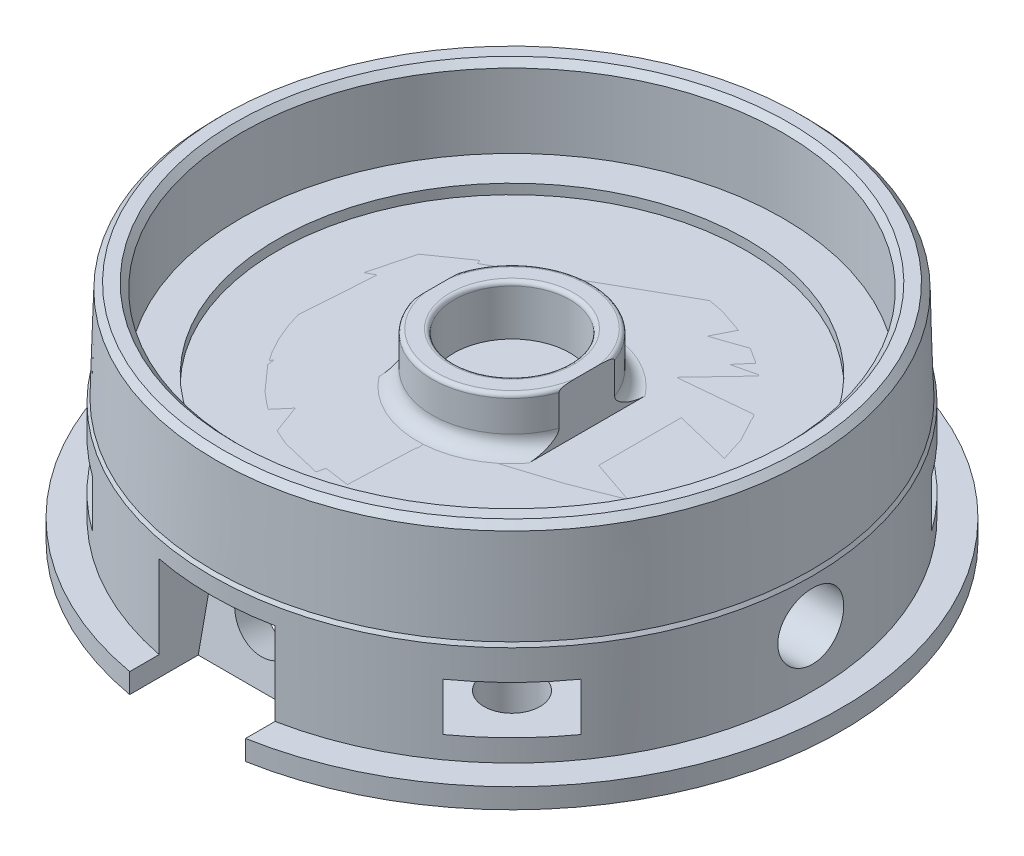
SolidWorks part; units mm, degrees
ref_plane "Front Plane" through (0, 0, 0) normal (0, 0, 1) x (1, 0, 0)
ref_plane "Top Plane" through (0, 0, 0) normal (0, 1, 0) x (1, 0, 0)
ref_plane "Right Plane" through (0, 0, 0) normal (1, 0, 0) x (0, 0, -1)
sketch "Sketch1" plane through (0, 0, 0) normal (0, 1, 0) x (1, 0, 0)
  circle A0 centre (0, 0) radius 15.05
  dimension "D1" = 30.1
extrude "Boss-Extrude1" add sketch "Sketch1" along normal blind 6.2
sketch "Sketch2" plane through (0, 6.2, 0) normal (0, 1, 0) x (1, 0, 0)
  circle A0 centre (0, 0) radius 11.75
  dimension "D1" = 23.5
extrude "Cut-Extrude1" cut sketch "Sketch2" against normal blind 0.5
sketch "Sketch3" plane through (0, 6.2, 0) normal (0, 1, 0) x (1, 0, 0)
  circle A0 centre (0, 0) radius 13.575
  circle A1 centre (0, 0) radius 15.05
  circle A2 centre (0, 0) radius 15.05 construction
  dimension "D1" = 27.15
extrude "Boss-Extrude2" add sketch "Sketch3" along normal blind 4
sketch "Sketch4" plane through (0, 5.7, 0) normal (0, 1, 0) x (1, 0, 0)
  circle A0 centre (0, 0) radius 1.65
  dimension "D1" = 3.3
extrude "Cut-Extrude2" cut sketch "Sketch4" against normal through all
ref_plane "Plane1" through (3.75, 0, 0) normal (1, 0, 0) x (0, 0, -1)
sketch "Sketch5" plane through (0, 0, 0) normal (1, 0, 0) x (0, 0, -1)
  line L1 (1.65, 5.7) -> (-1.65, 5.7) construction
  line L2 (-2.875, -0.05) -> (2.875, -0.05) construction
  line L3 (-2.875, -0.05) -> (-2.875, 5.7) construction
  line L4 (-2.875, 5.7) -> (2.875, 5.7) construction
  line L5 (2.875, -0.05) -> (2.875, 5.7) construction
  line L6 (-2.875, -0.05) -> (2.875, 5.7) construction
  line L7 (-2.875, 5.7) -> (2.875, -0.05) construction
  circle A0 centre (0, 2.825) radius 1.65
  dimension "D1" = 3.3
  dimension "D2" = 5.75
extrude "Cut-Extrude3" cut sketch "Sketch5" along normal through all
sketch "Sketch6" plane through (0, 0, 0) normal (0, -1, 0) x (1, 0, 0)
  circle A0 centre (0, 0) radius 1.65 construction
  circle A1 centre (0, 0) radius 1.65
  circle A2 centre (0, 0) radius 16.5
  dimension "D1" = 33
extrude "Boss-Extrude3" add sketch "Sketch6" along normal blind 1
sketch "Sketch7" plane through (3.75, 0, 0) normal (1, 0, 0) x (0, 0, -1)
  line L7 (-2.875, 5.7) -> (2.875, 5.7)
  line L8 (-2.875, 5.7) -> (-2.875, -0.05)
  line L9 (-2.875, -0.05) -> (2.875, -0.05)
  line L10 (2.875, 5.7) -> (2.875, -0.05)
  line L11 (-2.875, 5.7) -> (2.875, -0.05) construction
  line L12 (-2.875, -0.05) -> (2.875, 5.7) construction
  point P1 (0, 2.825)
  dimension "D2" = 5.75
extrude "Cut-Extrude4" cut sketch "Sketch7" along normal blind 1.85
ref_axis "Axis1" through (0, 10.2, 0) along (0, -1, 0)
pattern_circular "CirPattern1" count 2 over 360 about axis through (0, 10.2, 0) along (0, -1, 0) of "Cut-Extrude4", "Cut-Extrude3"
ref_plane "Plane2" through (0, 0, 0) normal (0, 0, 1) x (0, -1, 0)
ref_plane "Plane3" through (0, 0, 12.6) normal (0, 0, 1) x (0, -1, 0)
sketch "Sketch11" plane through (0, 0, 12.6) normal (0, 0, 1) x (0, -1, 0)
  line L0 (0, 23.2225) -> (0, -23.2225) construction
  point P4 (0, 0)
ref_plane "Plane4" through (0, 2.5624, 12.0553) normal (0, 0.2079, 0.9781) x (-1, 0, 0)
sketch "Sketch9" plane through (0, 0.4393, 12.5066) normal (0, 0.2079, 0.9781) x (0, -0.9781, 0.2079)
  line L0 (-12.1477, 0) -> (-2.1706, 0) construction
  line L2 (1.4491, 2.9) -> (-4.3509, 2.9) construction
  line L3 (1.4491, 2.9) -> (1.4491, -2.9) construction
  line L4 (1.4491, -2.9) -> (-4.3509, -2.9) construction
  line L5 (-4.3509, 2.9) -> (-4.3509, -2.9) construction
  line L6 (1.4491, 2.9) -> (-4.3509, -2.9) construction
  line L7 (1.4491, -2.9) -> (-4.3509, 2.9) construction
  line L8 (0.4491, 23.2225) -> (0.4491, -23.2225) construction
  circle A0 centre (-1.4509, 0) radius 1.65
  dimension "D2" = 3.3
  dimension "D1" = 5.8
  dimension "D3" = 1
extrude "Cut-Extrude5" cut sketch "Sketch9" along normal through all and the other way blind 2
sketch "Sketch10" plane through (0, 0.0203, 12.5957) normal (0, 0.2079, 0.9781) x (0, -0.9781, 0.2079)
  line L1 (1.0208, 2.9) -> (-4.7792, 2.9) construction
  line L2 (-4.7792, 2.9) -> (-4.7792, -2.9) construction
  line L3 (1.0208, -2.9) -> (-4.7792, -2.9) construction
  line L5 (1.0208, 2.9) -> (-4.7792, 2.9)
  line L6 (-4.7792, 2.9) -> (-4.7792, -2.9)
  line L7 (1.0208, -2.9) -> (-4.7792, -2.9)
  line L8 (1.0208, 2.9) -> (3.0208, 2.9)
  line L9 (3.0208, 2.9) -> (3.0208, -2.9)
  line L10 (3.0208, -2.9) -> (1.0208, -2.9)
  dimension "D1" = 2
extrude "Cut-Extrude6" cut sketch "Sketch10" along normal blind 1.8
ref_plane "Plane5" through (0, 2.2506, 10.5881) normal (0, 0.2079, 0.9781) x (-1, 0, 0)
sketch "Sketch13" plane through (0, 2.2506, 10.5881) normal (0, 0.2079, 0.9781) x (-1, 0, 0)
  line L0 (-2.0203, -0.0157) -> (-3.3435, 3.6197)
  line L1 (-3.3435, 3.6197) -> (3.3435, 3.6197)
  line L2 (3.3435, 3.6197) -> (2.0203, -0.0157)
  line L3 (0, 0.7197) -> (0, 3.6197) construction
  line L4 (-2.9, 3.6197) -> (2.9, 3.6197) construction
  circle A0 centre (0, 0.7197) radius 1.65 construction
  circle A1 centre (0, 0.7197) radius 1.65 construction
  circle A2 centre (0, 0.7197) radius 2.15 construction
  arc A3 (2.0203, -0.0157) -> (-2.0203, -0.0157) centre (0, 0.7197) cw
  dimension "D1" = 20
  dimension "D2" = 0.5
ref_plane "Plane6" through (0, 0, 0) normal (-1, 0, 0) x (0, -1, 0)
ref_plane "Plane7" through (0, 0, 15.05) normal (0, 0, 1) x (1, 0, 0)
sketch "Sketch14" plane through (0, 0, 0) normal (-1, 0, 0) x (0, -1, 0)
  line L0 (-3.1606, 10.3947) -> (3.3348, 0) construction
  line L3 (0.0673, 11.0808) -> (-3.1606, 10.3947) construction
  line L5 (-3.1606, 10.3947) -> (-0.9781, 0.1272) construction
  arc A0 (-3.1606, 10.3947) -> (3.3348, 0) centre (14.3667, 14.1202) ccw
  dimension "D1" = 70
sweep "Cut-Sweep1" cut profiles "Sketch13" path "Sketch14"
sketch "Sketch19" plane through (0, 0, 15.05) normal (0, 0, 1) x (1, 0, 0)
  line L0 (2.9, 5.0693) -> (-2.9, 5.0693) construction
  line L1 (2.9, 5.0693) -> (-2.9, 5.0693) construction
  line L2 (15.05, 0) -> (-15.05, 0) construction
  line L3 (2.9, 0) -> (-2.9, 0) construction
  line L4 (-2.9, 5.0693) -> (-2.9, 0) construction
  line L5 (2.9, 5.0693) -> (2.9, 0) construction
  line L6 (-2.9, 4.1501) -> (2.9, 4.1501)
  line L7 (2.9, 4.1501) -> (2.9, 0)
  line L8 (2.9, 0) -> (-2.9, 0)
  line L9 (-2.9, 0) -> (-2.9, 4.1501)
  spline S0 degree 3 poles (-0.1103, 0.7763) (0.2206, 0.7763) (0.4399, 0.8212) (0.8405, 0.99) (1.0254, 1.1159) (1.2534, 1.3496) (1.3227, 1.4364) (1.4409, 1.6193) (1.4906, 1.7158) (1.5713, 1.9192) (1.6017, 2.0256) (1.6413, 2.2394) (1.6508, 2.3479) (1.6481, 2.6783) (1.6048, 2.894) (1.4812, 3.1989) (1.4311, 3.2954) (1.313, 3.4783) (1.2443, 3.5654) (1.0179, 3.8015) (0.8351, 3.9301) (0.4362, 4.1039) (0.2169, 4.1502) (-0.1103, 4.15) (-0.221, 4.1383) (-0.434, 4.0932) (-0.5375, 4.06) (-0.8386, 3.9282) (-1.0184, 3.8015) (-1.2465, 3.5629) (-1.3137, 3.4774) (-1.4314, 3.2948) (-1.4822, 3.1968) (-1.5642, 2.9938) (-1.5952, 2.8896) (-1.6378, 2.6758) (-1.6492, 2.5653) (-1.6515, 2.2381) (-1.6107, 2.0182) (-1.4501, 1.6141) (-1.3285, 1.4262) (-1.1006, 1.193) (-1.0155, 1.1218) (-0.835, 0.9992) (-0.7396, 0.9474) (-0.5381, 0.8627) (-0.4321, 0.8302) (-0.2188, 0.7873) (-0.1103, 0.7763) (0.2206, 0.7763) (0.4399, 0.8212) knots -0.03125 -0.03125 0 0 0.0625 0.0625 0.125 0.125 0.15625 0.15625 0.1875 0.1875 0.21875 0.21875 0.25 0.25 0.3125 0.3125 0.34375 0.34375 0.375 0.375 0.4375 0.4375 0.5 0.5 0.53125 0.53125 0.5625 0.5625 0.625 0.625 0.65625 0.65625 0.6875 0.6875 0.71875 0.71875 0.75 0.75 0.8125 0.8125 0.875 0.875 0.90625 0.90625 0.9375 0.9375 0.96875 0.96875 1 1 1.0625 1.0625 1.125 only from (0, 0.7763) to (0, 0.7763) construction
  spline S1 degree 3 poles (-0.1103, 0.7763) (0.2206, 0.7763) (0.4399, 0.8212) (0.8405, 0.99) (1.0254, 1.1159) (1.2534, 1.3496) (1.3227, 1.4364) (1.4409, 1.6193) (1.4906, 1.7158) (1.5713, 1.9192) (1.6017, 2.0256) (1.6413, 2.2394) (1.6508, 2.3479) (1.6481, 2.6783) (1.6048, 2.894) (1.4812, 3.1989) (1.4311, 3.2954) (1.313, 3.4783) (1.2443, 3.5654) (1.0179, 3.8015) (0.8351, 3.9301) (0.4362, 4.1039) (0.2169, 4.1502) (-0.1103, 4.15) (-0.221, 4.1383) (-0.434, 4.0932) (-0.5375, 4.06) (-0.8386, 3.9282) (-1.0184, 3.8015) (-1.2465, 3.5629) (-1.3137, 3.4774) (-1.4314, 3.2948) (-1.4822, 3.1968) (-1.5642, 2.9938) (-1.5952, 2.8896) (-1.6378, 2.6758) (-1.6492, 2.5653) (-1.6515, 2.2381) (-1.6107, 2.0182) (-1.4501, 1.6141) (-1.3285, 1.4262) (-1.1006, 1.193) (-1.0155, 1.1218) (-0.835, 0.9992) (-0.7396, 0.9474) (-0.5381, 0.8627) (-0.4321, 0.8302) (-0.2188, 0.7873) (-0.1103, 0.7763) (0.2206, 0.7763) (0.4399, 0.8212) knots -0.03125 -0.03125 0 0 0.0625 0.0625 0.125 0.125 0.15625 0.15625 0.1875 0.1875 0.21875 0.21875 0.25 0.25 0.3125 0.3125 0.34375 0.34375 0.375 0.375 0.4375 0.4375 0.5 0.5 0.53125 0.53125 0.5625 0.5625 0.625 0.625 0.65625 0.65625 0.6875 0.6875 0.71875 0.71875 0.75 0.75 0.8125 0.8125 0.875 0.875 0.90625 0.90625 0.9375 0.9375 0.96875 0.96875 1 1 1.0625 1.0625 1.125 only from (0, 0.7763) to (0, 0.7763) construction
extrude "Cut-Extrude11" cut sketch "Sketch19" against normal up to surface (0.6098 mm away) up to face at (0, 2.0347, 14.0077)
pattern_circular "CirPattern2" count 2 over 360 about axis through (0, 10.2, 0) along (0, -1, 0) of "Cut-Extrude5", "Cut-Sweep1", "Cut-Extrude6", "Cut-Extrude11"
sketch "Sketch16" plane through (0, -1, 0) normal (0, -1, 0) x (1, 0, 0)
  line L0 (0, 0) -> (-11.6673, 11.6673) construction
  line L1 (0, 11.1539) -> (0, -11.1539) construction
  circle A0 centre (0, 0) radius 16.5 construction
  circle A1 centre (-8.5913, 8.5913) radius 1.4
  circle A2 centre (-8.5913, 8.5913) radius 2.9 construction
  circle A3 centre (0, 0) radius 15.05 construction
  dimension "D2" = 2.8
  dimension "D3" = 5.8
  dimension "D1" = 45
extrude "Cut-Extrude8" cut sketch "Sketch16" against normal blind 4.5
sketch "Sketch17" plane through (0, 3.5, 0) normal (0, -1, 0) x (1, 0, 0)
  line L1 (-10.5918, 10.5918) -> (-11.324, 7.8591) construction
  line L2 (-11.324, 7.8591) -> (-9.3236, 5.8587)
  line L3 (-9.3236, 5.8587) -> (-6.5909, 6.5909)
  line L4 (-6.5909, 6.5909) -> (-5.8587, 9.3236)
  line L5 (-5.8587, 9.3236) -> (-7.8591, 11.324)
  line L6 (-7.8591, 11.324) -> (-10.5918, 10.5918) construction
  line L7 (-7.8591, 11.324) -> (-8.9095, 12.3744)
  line L8 (-8.9095, 12.3744) -> (-12.3744, 8.9095)
  line L9 (-12.3744, 8.9095) -> (-11.324, 7.8591)
  line L10 (-6.5909, 6.5909) -> (-8.5913, 8.5913) construction
  circle A0 centre (-8.5913, 8.5913) radius 2.45 construction
  circle A1 centre (0, 0) radius 15.05 construction
  dimension "D1" = 4.9
extrude "Cut-Extrude9" cut sketch "Sketch17" along normal blind 2.4
pattern_circular "CirPattern3" count 4 over 360 about axis through (0, 10.2, 0) along (0, -1, 0) of "Cut-Extrude8", "Cut-Extrude9"
sketch "Sketch18" plane through (0, 5.7, 0) normal (0, 1, 0) x (1, 0, 0)
  circle A2 centre (0, 0) radius 2.9
  dimension "D1" = 5.8
extrude "Cut-Extrude10" cut sketch "Sketch18" against normal blind 0.7
sketch "Sketch20" plane through (0, 5.7, 0) normal (0, 1, 0) x (1, 0, 0)
  line L0 (3.75, 2.875) -> (3.75, -2.875) construction
  line L1 (-3.75, -2.875) -> (-3.75, 2.875) construction
  line L2 (3.75, 1.3919) -> (3.75, -1.3919)
  line L3 (-3.75, -1.3919) -> (-3.75, 1.3919)
  circle A0 centre (0, 0) radius 2.9 construction
  circle A1 centre (0, 0) radius 2.9
  arc A2 (3.75, 1.3919) -> (-3.75, 1.3919) centre (0, 0) ccw
  arc A3 (-3.75, -1.3919) -> (3.75, -1.3919) centre (0, 0) ccw
  dimension "D1" = 8
extrude "Boss-Extrude4" add sketch "Sketch20" along normal blind 2.5
fillet "Fillet2" radius 0.75 2 edges at (0, 5.7, 4) (0, 5.7, -4)
fillet "Fillet3" radius 0.2 3 edges at (0, 8.2, 4) (0, 8.2, -4) (0, 8.2, 2.9)
sketch "Sketch21" plane through (0, 0, 0) normal (0, 0, 1) x (1, 0, 0)
  line L0 (13.575, 6.2) -> (-13.575, 6.2) construction
  line L1 (13.575, 6.2) -> (-13.575, 6.2) construction
  line L2 (0, 0) -> (0, 10.2954) construction
  line L3 (0, 10.2) -> (0, 0) construction
  line L4 (-14.9, 10.2) -> (-15.05, 5) construction
  line L5 (15.05, 10.2) -> (-15.05, 10.2) construction
  line L6 (-15.05, 10.2) -> (-15.05, 4.475) construction
  line L7 (-15.05, 5) -> (-15.05, 10.2)
  line L8 (-15.05, 10.2) -> (-14.9, 10.2)
  line L10 (-14.9447, 5.1824) -> (-14.8, 10.2)
  line L11 (-14.8, 10.2) -> (-14.9, 10.2)
  line L14 (-15.05, 5) -> (-14.9447, 5.1824)
  dimension "D1" = 0.15
  dimension "D2" = 30
  dimension "D3" = 1.2
  dimension "D4" = 0.1
revolve "Cut-Revolve1" cut sketch "Sketch21" angle 360 about L2
chamfer "Chamfer1" distance 0.3 angle 45 1 edges at (0, 10.2, -14.8) first distance on face at (0, 10.2, 13.575)
sketch "Sketch22" plane through (0, 4.1501, 0) normal (0, -1, 0) x (1, 0, 0)
  line L0 (-2.9, 14.768) -> (2.9, 14.768)
  line L1 (2.9, 14.768) -> (2.9, 15.768)
  line L2 (2.9, 15.768) -> (-2.9, 15.768)
  line L3 (-2.9, 15.768) -> (-2.9, 14.768)
  line L4 (0, 0) -> (16.5, 0) construction
  line L5 (-2.9, -15.768) -> (-2.9, -14.768)
  line L6 (2.9, -15.768) -> (-2.9, -15.768)
  line L7 (2.9, -14.768) -> (2.9, -15.768)
  line L8 (-2.9, -14.768) -> (2.9, -14.768)
  circle A0 centre (0, 0) radius 16.5 construction
  dimension "D1" = 1
extrude "Cut-Extrude12" [suppressed] cut sketch "Sketch22" against normal blind 10
chamfer "Chamfer2" distance 0.3 angle 45 1 edges at (0, 10.2, 13.575)
sketch "Sketch23" plane through (0, 5.7, 0) normal (0, 1, 0) x (1, 0, 0)
  circle A0 centre (0, 0) radius 8.75
  dimension "D1" = 17.5
extrude "Boss-Extrude5" add sketch "Sketch23" against normal blind 5 separate body
sketch "Sketch24" plane through (0, -1, 0) normal (0, -1, 0) x (1, 0, 0)
  line L0 (0, 0) -> (16.5, 0) construction
  line L1 (-2.9, 13.7327) -> (2.9, 13.7327)
  line L2 (-2.9, 13.7327) -> (-2.9, 18.7327)
  line L3 (-2.9, 18.7327) -> (2.9, 18.7327)
  line L4 (2.9, 13.7327) -> (2.9, 18.7327)
  line L5 (2.9, -13.7327) -> (2.9, -18.7327)
  line L6 (-2.9, -18.7327) -> (2.9, -18.7327)
  line L7 (-2.9, -13.7327) -> (-2.9, -18.7327)
  line L8 (-2.9, -13.7327) -> (2.9, -13.7327)
  line L9 (-2.9, 12.8126) -> (-2.9, 14.6528) construction
  line L10 (2.9, 14.6528) -> (2.9, 12.8126) construction
  circle A1 centre (0, 0) radius 16.5 construction
  point P16 (0, 0)
  point P19 (0, 0)
  dimension "D1" = 5
extrude "Cut-Extrude13" cut sketch "Sketch24" against normal up to surface (1 mm away) up to face at (0, 0, 0)
fillet "Fillet4" radius 1 4 edges at (2.628, 0.6329, -10.932) (-2.628, 0.6329, -10.932) (2.628, 0.6329, 10.932) (-2.628, 0.6329, 10.932)
